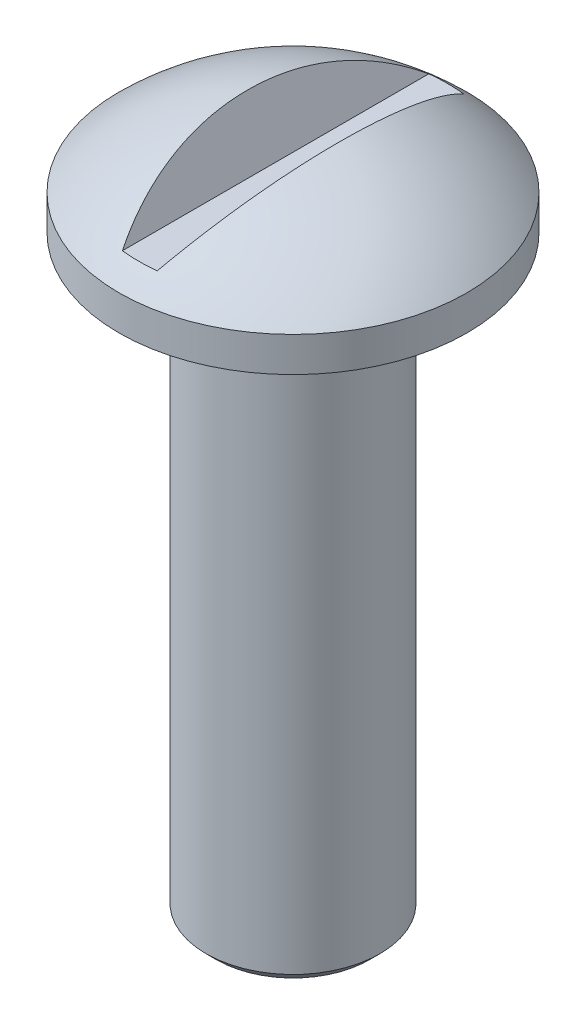
SolidWorks part; units mm, degrees
ref_plane "Front Plane" through (0, 0, 0) normal (0, 0, 1) x (1, 0, 0)
ref_plane "Top Plane" through (0, 0, 0) normal (0, 1, 0) x (1, 0, 0)
ref_plane "Right Plane" through (0, 0, 0) normal (1, 0, 0) x (0, 0, -1)
sketch "Sketch1" plane through (0, 0, 0) normal (0, 1, 0) x (1, 0, 0)
  circle A0 centre (0, 0) radius 12.7
  circle A1 centre (0, 0) radius 6.35
  dimension "D1" = 25.4
  dimension "D2" = 12.7
extrude "Boss-Extrude1" add sketch "Sketch1" against normal blind 43.18 contours A1
sketch "Sketch2" plane through (0, 0, 0) normal (0, 0, 1) x (1, 0, 0)
  line L0 (-14.6248, 7.62) -> (18.2672, 7.62) construction
  line L1 (0, 0) -> (0, -54.4938) construction
  line L2 (-6.35, -43.18) -> (6.35, -43.18) construction
  line L3 (0, -43.18) -> (-12.1179, -43.18) construction
  line L4 (0, 0) -> (0, 7.62) construction
  point P5 (0, -43.18)
  point P10 (0, 7.62)
  point P12 (0, 0)
  dimension "D1" = 50.8
extrude "Boss-Extrude2" add sketch "Sketch1<3>" along normal up to vertex (7.62 mm away) contours A0 up to point (0, 7.62, 0)
sketch "Sketch1<3>" plane through (0, 0, 0) normal (0, 1, 0) x (1, 0, 0) same geometry as "Sketch1"
sketch "Sketch3" plane through (0, 0, 0) normal (0, 0, 1) x (1, 0, 0)
  line L0 (0, 0) -> (0, 14.6831) construction
  line L1 (0, 2.54) -> (-12.7, 2.54) construction
  line L3 (0, 0) -> (-18.8118, 0) construction
  line L4 (-12.7, 7.62) -> (-12.7, 0) construction
  line L5 (-12.7, 10.0934) -> (-12.7, -3.1543) construction
  line L7 (-12.7, 2.54) -> (-15.2094, 2.54)
  line L8 (-15.2094, 2.54) -> (-15.2094, 10.3313)
  line L9 (-15.2094, 10.3313) -> (0, 10.3313)
  line L10 (0, 10.3313) -> (0, 7.62)
  line L11 (0, 3.81) -> (-18.8118, 3.81) construction
  arc A0 (-12.7, 2.54) -> (0, 7.62) centre (-0.2547, -10.1582) cw
  dimension "D2" = 17.78
  dimension "D1" = 2.54
  dimension "D3" = 3.81
revolve "Cut-Revolve1" cut sketch "Sketch3" angle 360 about L0
ref_plane "Plane1" through (0, 3.81, 0) normal (0, 1, 0) x (1, 0, 0)
sketch "Sketch4" plane through (0, 3.81, 0) normal (0, 1, 0) x (1, 0, 0)
  line L1 (-1.27, 16.9142) -> (1.27, 16.9142)
  line L2 (-1.27, 16.9142) -> (-1.27, -16.9142)
  line L3 (-1.27, -16.9142) -> (1.27, -16.9142)
  line L4 (1.27, 16.9142) -> (1.27, -16.9142)
  line L5 (-1.27, 16.9142) -> (1.27, -16.9142) construction
  line L6 (-1.27, -16.9142) -> (1.27, 16.9142) construction
  point P0 (0, 0)
  dimension "D1" = 2.54
extrude "Cut-Extrude1" cut sketch "Sketch4" along normal through all draft 30 draft outward yes
chamfer "Chamfer1" distance 0.762 angle 45 1 edges at (0, -43.18, 6.35)
